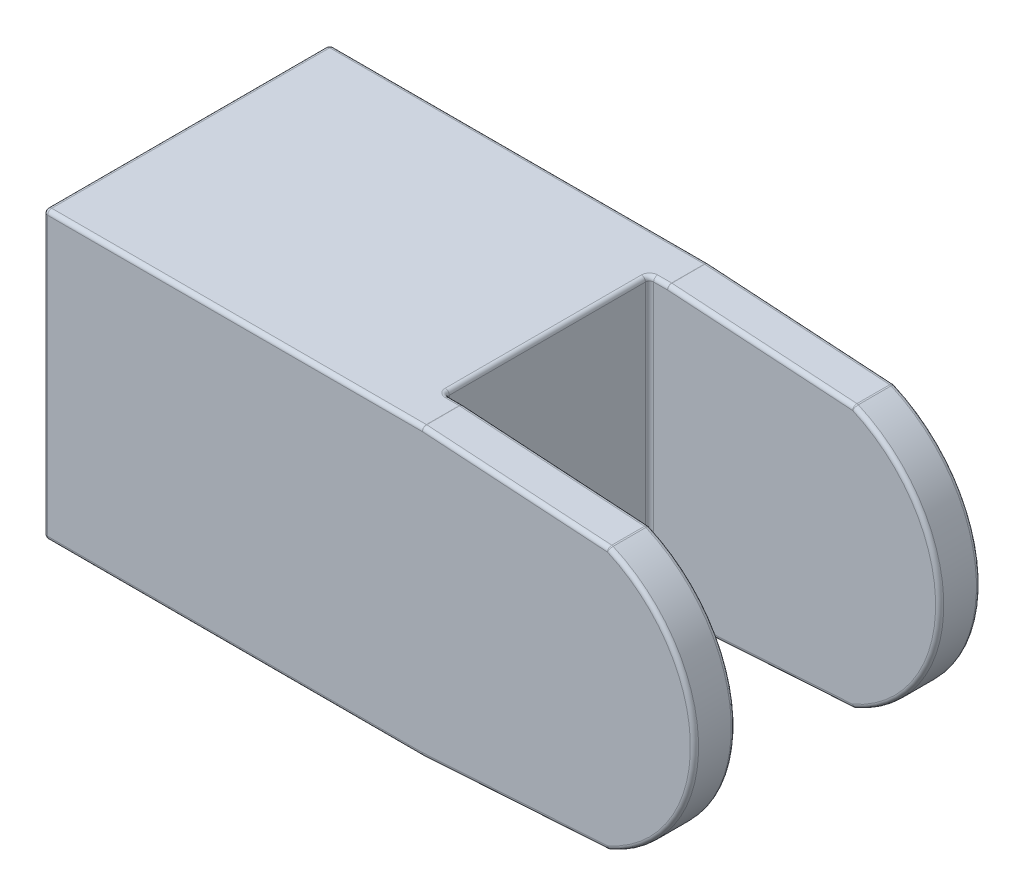
SolidWorks part; units mm, degrees
ref_plane "Plan de face" through (0, 0, 0) normal (0, 0, 1) x (1, 0, 0)
ref_plane "Plan de dessus" through (0, 0, 0) normal (0, 1, 0) x (1, 0, 0)
ref_plane "Plan de droite" through (0, 0, 0) normal (1, 0, 0) x (0, 0, -1)
sketch "Sketch2" plane through (0, 0, 0) normal (0, 1, 0) x (1, 0, 0)
  line L0 (0, 0) -> (0, 70)
  line L1 (0, 70) -> (159.2672, 70)
  line L2 (159.2672, 70) -> (159.2672, 60)
  line L3 (159.2672, 60) -> (88.2672, 60)
  line L4 (88.2672, 60) -> (88.2672, 10)
  line L5 (88.2672, 10) -> (159.2672, 10)
  line L6 (159.2672, 10) -> (159.2672, 0)
  line L7 (159.2672, 0) -> (0, 0)
  dimension "D1" = 70
  dimension "D2" = 10
  dimension "D3" = 71
extrude "Boss-Extrude1" add sketch "Sketch2" along normal mid plane 70
sketch "Sketch3" plane through (0, 0, 0) normal (0, 0, 1) x (1, 0, 0)
  line L0 (92.7127, 35) -> (159.2672, 30.7673)
  line L1 (0, 35) -> (159.2672, 35) construction
  line L2 (159.2672, 35) -> (159.2672, -35) construction
  line L3 (38.5, 0) -> (-38.5, 0) construction
  line L4 (92.7127, -35) -> (159.2672, -30.7673)
  line L5 (92.7127, 35) -> (159.2672, 35)
  line L6 (159.2672, 35) -> (159.2672, 30.7673)
  line L7 (92.7127, -35) -> (159.2672, -35)
  line L8 (159.2672, -35) -> (159.2672, -30.7673)
extrude "Cut-Extrude1" cut sketch "Sketch3" against normal blind 70
sketch "Sketch4" plane through (0, 0, 0) normal (0, 0, 1) x (1, 0, 0)
  line L0 (0, 35) -> (92.7127, 35) construction
  line L1 (0, -35) -> (92.7127, -35) construction
  line L2 (159.2672, 30.7673) -> (159.2672, -30.7673) construction
  arc A0 (124.2672, 35) -> (124.2672, -35) centre (124.2672, 0) cw
extrude "Cut-Extrude2" cut sketch "Sketch4" against normal blind 70 and the other way through all
fillet "Fillet3" radius 1 36 edges at (159.2672, 0, 0) (159.2672, 0, -70) (138.2005, 32.1071, -65) (138.2005, -32.1071, -5) (159.2672, 0, -10) (138.2005, -32.1071, -65) (159.2672, 0, -60) (115.4566, -33.5535, 0) (115.4566, -33.5535, -70) (92.7127, -35, -65) (115.4566, 33.5535, 0) (115.4566, 33.5535, -70) (92.7127, 35, -65) (115.4566, -33.5535, -60) (115.4566, -33.5535, -10) (115.4566, 33.5535, -60) (115.4566, 33.5535, -10) (46.3563, -35, 0) (90.49, -35, -10) (88.2672, -35, -35) (90.49, -35, -60) (46.3563, -35, -70) (0, -35, -35) (46.3563, 35, 0) (90.49, 35, -10) (88.2672, 35, -35) (90.49, 35, -60) (46.3563, 35, -70) (0, 35, -35) (0, 0, 0) (0, 0, -70) (88.2672, 0, -60) (88.2672, 0, -10) (92.7127, -35, -5) (92.7127, 35, -5) (138.2005, 32.1071, -5)
move or copy body "Body-Move/Copy1" bodies to move or copy 103 copy no translate (0, 0, 35)
sketch "Sketch5" plane through (0, 0, 0) normal (0, 0, 1) x (1, 0, 0)
  line L0 (0, 0) -> (-28.7617, 0) construction
